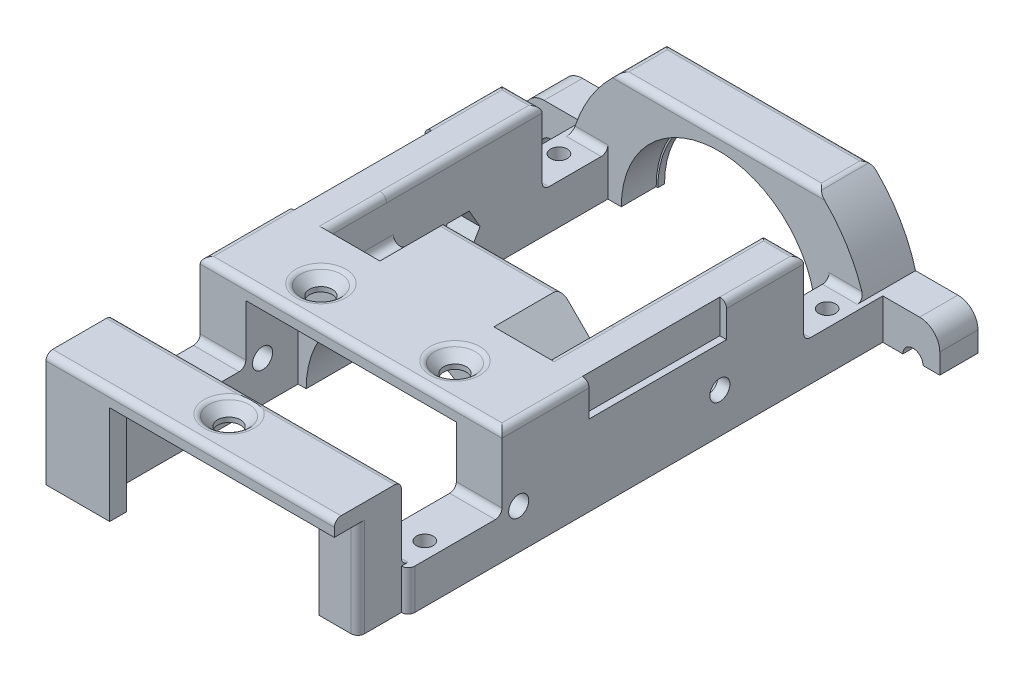
SolidWorks part; units mm, degrees
material "ABS"
ref_plane "Front" through (0, 0, 0) normal (0, 0, 1) x (1, 0, 0)
ref_plane "Top" through (0, 0, 0) normal (0, 1, 0) x (1, 0, 0)
ref_plane "Right" through (0, 0, 0) normal (1, 0, 0) x (0, 0, -1)
sketch "草图1" plane through (0, 0, 0) normal (0, 1, 0) x (1, 0, 0)
  line L1 (0, 0) -> (50, 0)
  line L2 (0, 0) -> (0, 92.5)
  line L3 (0, 92.5) -> (50, 92.5)
  line L4 (50, 0) -> (50, 92.5)
  dimension "D1" = 50
  dimension "D2" = 92.5
extrude "凸台-拉伸1" add sketch "草图1" along normal blind 20
sketch "草图3" plane through (0, 0, 0) normal (0, -1, 0) x (1, 0, 0)
  line L0 (0, 0) -> (50, 0) construction
  line L1 (9.3, -2.5) -> (40.7, -2.5)
  line L2 (9.3, -2.5) -> (9.3, -31.8)
  line L3 (9.3, -31.8) -> (40.7, -31.8)
  line L4 (40.7, -2.5) -> (40.7, -31.8)
  point P6 (25, -2.5)
  point P7 (25, 0)
  dimension "D1" = 2.5
  dimension "D2" = 31.4
  dimension "D3" = 29.3
extrude "切除-拉伸1" cut sketch "草图3" against normal blind 14.5
sketch "草图21" plane through (0, 0, 0) normal (0, -1, 0) x (1, 0, 0)
  line L1 (2.5, 0) -> (47.5, 0)
  line L2 (2.5, 0) -> (2.5, -92.5)
  line L3 (2.5, -92.5) -> (47.5, -92.5)
  line L4 (47.5, 0) -> (47.5, -92.5)
  line L5 (2.5, 0) -> (47.5, -92.5) construction
  line L6 (2.5, -92.5) -> (47.5, 0) construction
  point P0 (25, -46.25)
  dimension "D1" = 92.5
  dimension "D2" = 45
extrude "切除-拉伸16" cut sketch "草图21" against normal blind 53 flip side to cut
sketch "草图4" plane through (0, 0, -31.8) normal (0, 0, 1) x (1, 0, 0)
  line L0 (9.3, 0) -> (40.7, 0) construction
  line L1 (10.5, 0) -> (39.5, 0)
  arc A0 (39.5, 0) -> (10.5, 0) centre (25, 0) ccw
  dimension "D1" = 29
extrude "切除-拉伸2" cut sketch "草图4" against normal blind 15
fillet "圆角6" radius 1 4 edges at (25, 20, 0) (2.5, 20, -46.25) (25, 20, -92.5) (47.5, 20, -46.25)
sketch "草图5" plane through (0, 0, -46.8) normal (0, 0, 1) x (1, 0, 0)
  line L0 (10.5, 0) -> (39.5, 0) construction
  line L1 (8.5, 0) -> (41.5, 0)
  arc A0 (41.5, 0) -> (8.5, 0) centre (25, 0) ccw
  dimension "D1" = 33
extrude "切除-拉伸3" cut sketch "草图5" against normal blind 30
sketch "草图6" plane through (0, 0, -76.8) normal (0, 0, 1) x (1, 0, 0)
  line L0 (8.5, 0) -> (41.5, 0) construction
  line L1 (7.5, 0) -> (42.5, 0)
  arc A0 (42.5, 0) -> (7.5, 0) centre (25, 0) ccw
  dimension "D1" = 35
extrude "切除-拉伸4" cut sketch "草图6" against normal blind 9
sketch "草图7" plane through (0, 0, 0) normal (0, -1, 0) x (1, 0, 0)
  line L1 (41.5, -46.8) -> (8.5, -46.8)
  line L2 (41.5, -46.8) -> (41.5, -76.8)
  line L3 (41.5, -76.8) -> (8.5, -76.8)
  line L4 (8.5, -46.8) -> (8.5, -76.8)
extrude "切除-拉伸5" cut sketch "草图7" against normal through all
sketch "草图8" plane through (0, 0, -85.8) normal (0, 0, 1) x (1, 0, 0)
  line L0 (7.5, 0) -> (42.5, 0) construction
  circle A0 centre (25, 0) radius 16
  dimension "D1" = 32
extrude "切除-拉伸6" cut sketch "草图8" against normal blind 2.5
sketch "草图9" plane through (0, 0, 0) normal (0, -1, 0) x (1, 0, 0)
  line L0 (47.5, -92.5) -> (47.5, 0) construction
  line L2 (2.5, 0) -> (47.5, 0) construction
  circle A0 centre (45, -15) radius 1.25
  dimension "D1" = 2.5
  dimension "D2" = 2.5
  dimension "D3" = 15
extrude "切除-拉伸7" cut sketch "草图9" against normal through all
pattern_linear "阵列(线性)1" count 2 spacing 60 along (0, 0, -1) count 2 spacing 40 along (-1, 0, 0) of "切除-拉伸7"
sketch "草图10" plane through (0, 14.5, 0) normal (0, -1, 0) x (1, 0, 0)
  line L0 (40.7, -2.5) -> (9.3, -2.5) construction
  line L1 (25, -5.8) -> (25, -75.3486) construction
  line L2 (2.5, 0) -> (47.5, 0) construction
  circle A0 centre (25, -5.8) radius 1.5
  circle A1 centre (35, -29.5) radius 1.5
  circle A2 centre (15, -29.5) radius 1.5
  point P11 (25, 0)
  dimension "D2" = 3
  dimension "D6" = 20
  dimension "D1" = 3.3
  dimension "D5" = 23.7
sketch "草图13" plane through (0, 20, 0) normal (0, 1, 0) x (1, 0, 0)
  line L0 (46.5, 91.5) -> (3.5, 91.5) construction
  line L1 (-1, 81) -> (51, 81)
  line L2 (-1, 81) -> (-1, 69)
  line L3 (-1, 69) -> (51, 69)
  line L4 (51, 81) -> (51, 69)
  line L5 (25, -908.5) -> (25, 49091.5) construction
  line L7 (-1, 24) -> (51, 24)
  line L8 (-1, 24) -> (-1, 10)
  line L9 (-1, 10) -> (51, 10)
  line L10 (51, 24) -> (51, 10)
  circle A0 centre (5, 75) radius 1.25 construction
  circle A1 centre (5, 15) radius 1.25 construction
  point P7 (25, 81)
  point P17 (25, 91.5)
  point P18 (25, 24)
  dimension "D1" = 6
  dimension "D2" = 12
  dimension "D3" = 9
  dimension "D4" = 14
  dimension "D5" = 52
extrude "切除-拉伸10" cut sketch "草图13" against normal blind 14
extrude "切除-拉伸8" cut sketch "草图10" against normal through all
sketch "草图11" plane through (0, 0, -2.5) normal (0, 0, -1) x (-1, 0, 0)
  line L1 (-13, 0) -> (-37, 0)
  line L2 (-13, 0) -> (-13, 12)
  line L3 (-13, 12) -> (-37, 12)
  line L4 (-37, 0) -> (-37, 12)
  line L5 (-40.7, 0) -> (-9.3, 0) construction
  point P6 (-25, 0)
  point P7 (-25, 0)
  dimension "D1" = 24
  dimension "D2" = 12
extrude "切除-拉伸9" cut sketch "草图11" against normal through all
fillet "圆角2" [suppressed] radius 2
fillet "圆角3" [suppressed] radius 2
sketch "草图15" plane through (0, 20, 0) normal (0, 1, 0) x (1, 0, 0)
  line L1 (2.5, 0) -> (13, 0) construction
  line L2 (2.5, 24) -> (2.5, 69) construction
  circle A0 centre (7.5, 25) radius 1.5
  dimension "D1" = 3
  dimension "D2" = 5
  dimension "D3" = 25
extrude "切除-拉伸12" [suppressed] cut sketch "草图15" against normal blind 6
sketch "草图16" plane through (0, 0, 0) normal (0, 0, 1) x (1, 0, 0)
  line L6 (49, 0) -> (49, 14.5)
  line L7 (37, 0) -> (47.5, 0) construction
  line L8 (49, 14.5) -> (13, 14.5)
  line L9 (13, 14.5) -> (13, 0)
  line L10 (13, 0) -> (49, 0)
  line L11 (37, 12) -> (37, 0) construction
  line L16 (13, 0) -> (13, 12) construction
  dimension "D1" = 12
  dimension "D2" = 14.5
extrude "切除-拉伸13" cut sketch "草图16" against normal blind 3.5
ref_plane "基准面1" through (25, 0, 0) normal (1, 0, 0) x (0, 0, -1)
mirror "镜向1" [suppressed] about plane through (25, 0, 0) normal (1, 0, 0)
sketch "草图22" plane through (0, 20, 0) normal (0, 1, 0) x (1, 0, 0)
  line L0 (47.5, 0) -> (2.5, 0) construction
  line L1 (11.5, 33) -> (38.5, 33)
  line L2 (11.5, 33) -> (11.5, 0)
  line L3 (11.5, 0) -> (38.5, 0)
  line L4 (38.5, 33) -> (38.5, 0)
  circle A0 centre (15, 29.5) radius 1.5 construction
  circle A1 centre (35, 29.5) radius 1.5 construction
  dimension "D3" = 3.5
  dimension "D1" = 3.5
  dimension "D2" = 3.5
extrude "切除-拉伸17" cut sketch "草图22" against normal blind 3
sketch "草图24" plane through (0, 0, -92.5) normal (0, 0, -1) x (-1, 0, 0)
  line L0 (-46.5, 20) -> (-3.5, 20) construction
  line L1 (-47.5, 19) -> (-47.5, 0) construction
  line L2 (-2.5, 19) -> (-2.5, 0) construction
  circle A0 centre (-43, 14) radius 1.5
  circle A1 centre (-7, 14) radius 1.5
  dimension "D3" = 4.5
  dimension "D1" = 6
  dimension "D2" = 4.5
extrude "切除-拉伸19" [suppressed] cut sketch "草图24" against normal blind 18.6219 contours A1 | A0
hole_wizard "打孔尺寸(%根据十字)槽沉头木螺钉的类型1" positions "3D草图1" profile "草图25" countersink size "M3" standard "GB"
sketch3d "3D草图1"
  line L0 (25, 17, -5.8) -> (25, 14.5, -5.8) construction
  line L1 (35, 17, -29.5) -> (35, 14.5, -29.5) construction
  line L2 (15, 17, -29.5) -> (15, 14.5, -29.5) construction
  point P0 (25, 17, -5.8)
  point P4 (35, 17, -29.5)
  point P8 (15, 17, -29.5)
sketch "草图25" plane through (25, 17, -5.8) normal (1, 0, 0) x (0, 0, 1)
  line L0 (0, 0) -> (0, 14.5215)
  line L1 (0, 14.5215) -> (1.7, 13.5)
  line L2 (1.7, 13.5) -> (1.7, 1.6)
  line L3 (1.7, 1.6) -> (3.3, 0)
  line L5 (3.3, 0) -> (0, 0)
  line L6 (-1.7, 1.6) -> (-3.3, 0) construction
  line L10 (0, 14.5215) -> (-1.7, 13.5) construction
  line L11 (0, -6.35) -> (0, 107.95) construction
  dimension "孔直径" = 3.4
  dimension "孔深度" = 13.5
  dimension "近端锥形沉头孔直径" = 6.6
  dimension "近端锥形沉头孔角度" = 90
  dimension "导头角度" = 118
sketch "草图26" plane through (0, 20, 0) normal (0, 1, 0) x (1, 0, 0)
  line L1 (2.5, 92.5) -> (47.5, 92.5)
  line L2 (2.5, 92.5) -> (2.5, 0)
  line L3 (2.5, 0) -> (47.5, 0)
  line L4 (47.5, 92.5) -> (47.5, 0)
extrude "切除-拉伸21" cut sketch "草图26" against normal blind 3
fillet "圆角7" radius 1 23 edges at (47.5, 17, -5) (25, 17, 0) (2.5, 17, -5) (25, 17, -10) (25, 17, -2.5) (15, 17, -26.2) (35, 17, -26.2) (5.5, 17, -69) (8.5, 17, -57.9) (25, 17, -46.8) (41.5, 17, -57.9) (44.5, 17, -69) (47.5, 17, -46.5) (25, 17, -24) (2.5, 17, -46.5) (2.5, 17, -86.75) (25, 17, -92.5) (47.5, 17, -86.75) (20.8467, 17, -83.4) (29.1533, 17, -83.4) (25, 17, -85.8) (38.3267, 17, -81) (11.6733, 17, -81)
sketch "草图27" plane through (0, 0, -92.5) normal (0, 0, -1) x (-1, 0, 0)
  line L0 (-25, 16) -> (-25, 0) construction
  line L1 (-8.5, 16) -> (-41.5, 16) construction
  line L2 (-2.5, 5) -> (6, 5)
  line L3 (-2.5, 16) -> (-2.5, 0) construction
  line L4 (-47.5, 5) -> (-56, 5)
  line L5 (6, 5) -> (6, 0)
  line L6 (-56, 5) -> (-56, 0)
  line L7 (6, 0) -> (3, 0)
  line L8 (-56, 0) -> (-53, 0)
  line L9 (0, 0) -> (-2.5, 0)
  line L10 (-2.5, 5) -> (-2.5, 0)
  line L11 (-47.5, 5) -> (-47.5, 0)
  line L12 (-50, 0) -> (-47.5, 0)
  arc A0 (3, 0) -> (0, 0) centre (1.5, 0) ccw
  arc A1 (-53, 0) -> (-50, 0) centre (-51.5, 0) cw
  dimension "D2" = 3
  dimension "D1" = 62
  dimension "D3" = 53
  dimension "D4" = 5
extrude "凸台-拉伸2" add sketch "草图27" against normal blind 4
fillet "圆角8" radius 3 2 edges at (-6, 5, -90.5) (56, 5, -90.5)
sketch "草图31" plane through (0, 0, 0) normal (0, -1, 0) x (1, 0, 0)
  line L0 (25, -5.8) -> (25, -24) construction
  line L1 (9.3, -24) -> (40.7, -24) construction
  line L2 (47.5, 0) -> (47.5, -10)
  line L3 (2.5, 0) -> (3.5, 0)
  line L4 (2.5, 0) -> (2.5, -10)
  line L5 (2.5, -10) -> (3.5, -10)
  line L6 (3.5, 0) -> (3.5, -10)
  line L7 (47.5, 0) -> (46.5, 0)
  line L8 (46.5, 0) -> (46.5, -10)
  line L9 (47.5, -10) -> (46.5, -10)
  line L19 (2.5, 0) -> (2.5, -88.5) construction
  line L20 (2.5, -57.5) -> (3.5, -57.5)
  line L21 (2.5, -57.5) -> (2.5, -37)
  line L22 (2.5, -37) -> (3.5, -37)
  line L23 (3.5, -57.5) -> (3.5, -37)
  line L24 (47.5, -57.5) -> (47.5, -37)
  line L25 (47.5, -57.5) -> (46.5, -57.5)
  line L26 (46.5, -57.5) -> (46.5, -37)
  line L27 (47.5, -37) -> (46.5, -37)
  line L29 (50, -92.5) -> (0, -92.5) construction
  line L30 (2.5, 0) -> (13, 0) construction
  point P28 (25, -92.5)
  point P29 (7.75, 0)
  dimension "D1" = 10
  dimension "D2" = 1
  dimension "D3" = 37
  dimension "D4" = 35
extrude "切除-拉伸24" cut sketch "草图31" against normal blind 29
sketch "草图33" plane through (0, 0, -46.8) normal (0, 0, -1) x (-1, 0, 0)
  line L0 (-41.5, 9) -> (-33.5, 17)
  line L1 (-46.5, 17) -> (-3.5, 17) construction
  line L2 (-33.5, 17) -> (-41.5, 17)
  line L3 (-41.5, 17) -> (-41.5, 9)
  line L4 (-41.5, 16) -> (-41.5, 0) construction
  line L5 (-41.5, 16) -> (-41.5, 0) construction
  line L6 (-25, 16) -> (-25, 0) construction
  line L7 (-8.5, 16) -> (-41.5, 16) construction
  line L8 (-8.5, 17) -> (-8.5, 9)
  line L9 (-16.5, 17) -> (-8.5, 17)
  line L10 (-8.5, 9) -> (-16.5, 17)
  dimension "D1" = 45
  dimension "D2" = 8
extrude "切除-拉伸25" cut sketch "草图33" against normal blind 10
fillet "圆角9" radius 1 13 edges at (44.4696, 6, -81) (44.5, 6, -69) (5.5, 6, -69) (5.5304, 6, -81) (6.4, 6, -10) (2.5, 3, -10) (46.5, 7.25, -3.5) (47.5, 3, -10) (8.5, 17, -41.3) (8.5, 9, -41.8) (41.5, 17, -41.3) (41.5, 9, -41.8) (43.6, 6, -10)
ref_plane "基准面2" through (25, 0, 0) normal (1, 0, 0) x (0, 0, -1)
sketch "草图34" plane through (0, 0, 0) normal (0, -1, 0) x (1, 0, 0)
  line L0 (41.5, -76.8) -> (42.5, -76.8) construction
  line L1 (-18.4781, -115.4061) -> (59.8461, -115.4061)
  line L2 (-18.4781, -115.4061) -> (-18.4781, -76.8)
  line L3 (-18.4781, -76.8) -> (59.8461, -76.8)
  line L4 (59.8461, -115.4061) -> (59.8461, -76.8)
  line L5 (-18.4781, -115.4061) -> (59.8461, -76.8) construction
  line L6 (-18.4781, -76.8) -> (59.8461, -115.4061) construction
  point P0 (20.684, -96.103)
  point P7 (42, -76.8)
  dimension "D1" = 0
extrude "切除-拉伸26" cut sketch "草图34" against normal blind 20
sketch "草图35" plane through (0, 0, -76.8) normal (0, 0, -1) x (-1, 0, 0)
  line L0 (-2.5, 0) -> (-2.5, 6) construction
  line L1 (-47.5, 0) -> (-2.5, 0)
  line L2 (-47.5, 0) -> (-47.5, 17)
  line L3 (-47.5, 17) -> (-2.5, 17)
  line L4 (-2.5, 0) -> (-2.5, 17)
  line L5 (-7.5, 17) -> (-16.5, 17) construction
  dimension "D1" = 0
  dimension "D2" = 0
extrude "凸台-拉伸3" add sketch "草图35" along normal blind 9.7
sketch "草图36" plane through (47.5, 0, 0) normal (1, 0, 0) x (0, 0, -1)
  line L0 (86.5, 17) -> (76.8, 17) construction
  line L1 (76.8, 6) -> (80.8, 6)
  line L2 (76.8, 6) -> (76.8, 17)
  line L3 (76.8, 17) -> (80.8, 17)
  line L4 (80.8, 6) -> (80.8, 17)
  dimension "D1" = 4
extrude "切除-拉伸27" cut sketch "草图36" against normal through all
sketch "草图37" plane through (0, 0, -86.5) normal (0, 0, -1) x (-1, 0, 0)
  line L0 (-47.5, 0) -> (-2.5, 0) construction
  circle A0 centre (-25, 0) radius 22.5
  circle A1 centre (-25, 0) radius 33.0541
extrude "切除-拉伸28" cut sketch "草图37" against normal up to surface (5.7 mm away) up to face at (25, 11.5, -80.8)
ref_plane "基准面3" through (25, 0, 0) normal (1, 0, 0) x (0, 0, -1)
sketch "草图39" plane through (0, 0, -86.5) normal (0, 0, -1) x (-1, 0, 0)
  line L0 (-47.5, 0) -> (-2.5, 0) construction
  line L1 (-56, 0) -> (6, 0)
  line L2 (-56, 0) -> (-56, 6)
  line L3 (-56, 6) -> (6, 6)
  line L4 (6, 0) -> (6, 6)
  line L5 (-25, 8.8) -> (-25, -8.8) construction
  dimension "D1" = 62
  dimension "D2" = 0
  dimension "D3" = 6
  dimension "D4" = 31
extrude "凸台-拉伸4" add sketch "草图39" against normal up to surface (5.7 mm away) up to face at (47.296, 4.0092, -80.8)
sketch "草图40" plane through (0, 6, 0) normal (0, 1, 0) x (1, 0, 0)
  line L0 (3.3148, 80.8) -> (46.6852, 80.8) construction
  line L1 (8.5, 76.8) -> (41.5, 76.8)
  line L2 (8.5, 76.8) -> (8.5, 80.8)
  line L3 (8.5, 80.8) -> (41.5, 80.8)
  line L4 (41.5, 76.8) -> (41.5, 80.8)
  line L5 (41.5, 76.8) -> (41.5, 70) construction
  dimension "D1" = 0
extrude "切除-拉伸29" cut sketch "草图40" against normal blind 9.7
sketch "草图41" plane through (0, 0, -80.8) normal (0, 0, 1) x (1, 0, 0)
  line L0 (8.5, 0) -> (41.5, 0) construction
  circle A0 centre (25, 0) radius 14.5
  dimension "D1" = 29
extrude "切除-拉伸30" cut sketch "草图41" against normal blind 3.2
sketch "草图42" plane through (0, 0, -80.8) normal (0, 0, 1) x (1, 0, 0)
  line L7 (8.5, 0) -> (10.5, 0)
  line L8 (39.5, 0) -> (41.5, 0)
  line L9 (41.5, 0) -> (41.5, 6)
  line L10 (41.5, 6) -> (46.6852, 6)
  line L11 (39.7394, 17) -> (10.2606, 17)
  line L12 (3.3148, 6) -> (8.5, 6)
  line L13 (8.5, 6) -> (8.5, 0)
  line L14 (8.5, 0) -> (10.5, 0)
  line L15 (39.5, 0) -> (41.5, 0)
  line L16 (41.5, 0) -> (41.5, 6)
  line L17 (41.5, 6) -> (46.6852, 6)
  line L18 (39.7394, 17) -> (10.2606, 17)
  line L19 (3.3148, 6) -> (8.5, 6)
  line L20 (8.5, 6) -> (8.5, 0)
  arc A3 (39.5, 0) -> (10.5, 0) centre (25, 0) ccw
  arc A4 (46.6852, 6) -> (39.7394, 17) centre (25, 0) ccw
  arc A5 (10.2606, 17) -> (3.3148, 6) centre (25, 0) ccw
  arc A6 (39.5, 0) -> (10.5, 0) centre (25, 0) ccw
  arc A7 (46.6852, 6) -> (39.7394, 17) centre (25, 0) ccw
  arc A8 (10.2606, 17) -> (3.3148, 6) centre (25, 0) ccw
  dimension "D1" = 0
extrude "凸台-拉伸5" add sketch "草图42" along normal blind 2
sketch "草图43" plane through (0, 0, -86.5) normal (0, 0, -1) x (-1, 0, 0)
  line L0 (-56, 0) -> (6, 0) construction
  line L1 (-25, 8.8) -> (-25, -8.8) construction
  circle A0 centre (2, 0) radius 1.5
  dimension "D1" = 3
  dimension "D2" = 0
  dimension "D3" = 27
extrude "切除-拉伸31" cut sketch "草图43" against normal blind 6
mirror "镜向3" about plane through (25, 0, 0) normal (1, 0, 0) of "切除-拉伸31"
sketch "草图44" plane through (0, 0, -86.5) normal (0, 0, -1) x (-1, 0, 0)
  line L0 (-50.5, 0) -> (0.5, 0) construction
  circle A0 centre (-25, 0) radius 14.25
  dimension "D1" = 28.5
extrude "切除-拉伸32" cut sketch "草图44" against normal blind 6
fillet "圆角10" radius 3 2 edges at (56, 6, -83.65) (-6, 6, -83.65)
fillet "圆角11" radius 1 5 edges at (44.0926, 6, -78.8) (25, 17, -78.8) (10.2606, 17, -82.65) (39.7394, 17, -82.65) (25, 17, -86.5)
sketch "草图45" plane through (3.5, 0, 0) normal (-1, 0, 0) x (0, 0, 1)
  line L0 (-37, 17) -> (-37, 0) construction
  line L1 (-57.5, 0) -> (-37, 0)
  line L2 (-57.5, 0) -> (-57.5, 12)
  line L3 (-57.5, 12) -> (-37, 12)
  line L4 (-37, 0) -> (-37, 12)
  line L5 (-11, 0) -> (-37, 0) construction
  dimension "D1" = 12
extrude "凸台-拉伸7" add sketch "草图45" along normal blind 1
mirror "镜向4" about plane through (25, 0, 0) normal (1, 0, 0) of "凸台-拉伸7"
sketch "草图46" plane through (2.5, 0, 0) normal (-1, 0, 0) x (0, 0, 1)
  line L0 (-11, 0) -> (-80.8, 0) construction
  line L1 (-86.5, 16) -> (-86.5, 6) construction
  circle A0 centre (-56.5, 6) radius 1.5
  dimension "D1" = 6
  dimension "D2" = 3
  dimension "D3" = 30
extrude "切除-拉伸33" cut sketch "草图46" against normal through all
sketch "草图47" plane through (2.5, 0, 0) normal (-1, 0, 0) x (0, 0, 1)
  line L0 (-11, 0) -> (-80.8, 0) construction
  circle A0 centre (-26.5, 6) radius 1.5
  circle A1 centre (-56.5, 6) radius 1.5 construction
  dimension "D1" = 3
  dimension "D2" = 6
  dimension "D3" = 30
extrude "切除-拉伸34" cut sketch "草图47" against normal through all
sketch "草图48" plane through (8.5, 0, 0) normal (-1, 0, 0) x (0, 0, 1)
  line L1 (-53.2668, 6) -> (-54.8834, 8.8)
  line L2 (-54.8834, 8.8) -> (-58.1166, 8.8)
  line L3 (-58.1166, 8.8) -> (-59.7332, 6)
  line L4 (-59.7332, 6) -> (-58.1166, 3.2)
  line L5 (-58.1166, 3.2) -> (-54.8834, 3.2)
  line L6 (-54.8834, 3.2) -> (-53.2668, 6)
  circle A0 centre (-56.5, 6) radius 2.8 construction
  dimension "D1" = 5.6
fillet "圆角12" radius 1 2 edges at (5.9, 6, -24) (44.1, 6, -24)
sketch "草图49" plane through (0, 14.5, 0) normal (0, -1, 0) x (1, 0, 0)
  line L1 (9.3, -31.8) -> (40.7, -31.8)
  line L2 (9.3, -31.8) -> (9.3, -24)
  line L3 (9.3, -24) -> (40.7, -24)
  line L4 (40.7, -31.8) -> (40.7, -24)
  line L12 (46.5, -4.5) -> (46.5, 0)
  line L13 (46.5, 0) -> (13, 0)
  line L14 (13, 0) -> (13, -2.5)
  line L15 (13, -2.5) -> (9.3, -2.5)
  line L16 (9.3, -2.5) -> (9.3, -10)
  line L17 (9.3, -10) -> (40.7, -10)
  line L18 (40.7, -10) -> (40.7, -3.5)
  line L19 (40.7, -3.5) -> (45.5, -3.5)
  line L20 (46.5, -4.5) -> (46.5, 0)
  line L21 (46.5, 0) -> (13, 0)
  line L22 (13, 0) -> (13, -2.5)
  line L23 (13, -2.5) -> (9.3, -2.5)
  line L24 (9.3, -2.5) -> (9.3, -10)
  line L25 (9.3, -10) -> (40.7, -10)
  line L26 (40.7, -10) -> (40.7, -3.5)
  line L27 (40.7, -3.5) -> (45.5, -3.5)
  arc A1 (46.5, -4.5) -> (45.5, -3.5) centre (45.5, -4.5) ccw
  arc A2 (46.5, -4.5) -> (45.5, -3.5) centre (45.5, -4.5) ccw
  dimension "D1" = 0
extrude "切除-拉伸36" cut sketch "草图49" against normal blind 0.2
extrude "切除-拉伸37" cut sketch "草图48" along normal blind 4.2 and the other way blind 37.2
chamfer "倒角1" distance 1.5 angle 45 1 edges at (25, 14.25, -86.5)
